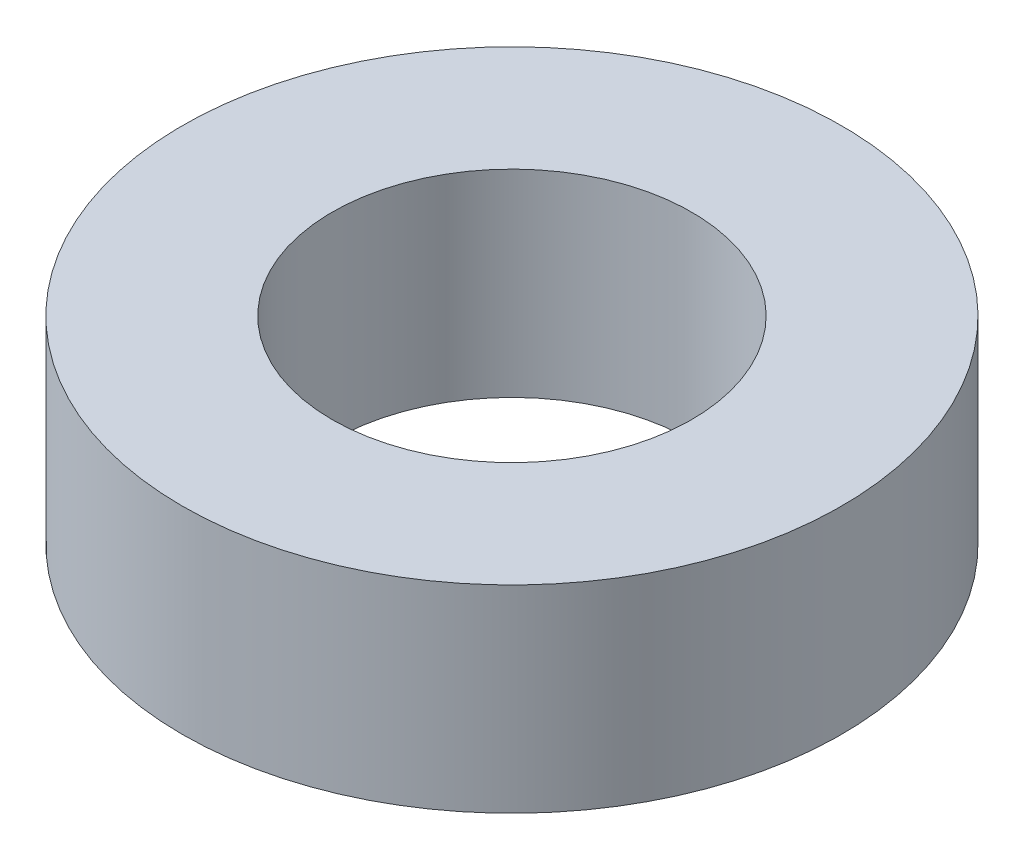
SolidWorks part; units mm, degrees
ref_plane "Front Plane" through (0, 0, 0) normal (0, 0, 1) x (1, 0, 0)
ref_plane "Top Plane" through (0, 0, 0) normal (0, 1, 0) x (1, 0, 0)
ref_plane "Right Plane" through (0, 0, 0) normal (1, 0, 0) x (0, 0, -1)
ref_axis "X-Axis" through (88.99, 0, 0) along (-1, 0, 0)
ref_axis "Y-Axis" through (0, 0, -88.99) along (0, 0, 1)
ref_axis "Z-Axis" through (0, -55, 0) along (0, 1, 0)
sketch "Sketch1" plane through (0, 0, 0) normal (0, 1, 0) x (1, 0, 0)
  circle A0 centre (0, 0) radius 6
  circle A1 centre (0, 0) radius 11
  dimension "D1" = 22
  dimension "D2" = 12
extrude "Boss-Extrude1" add sketch "Sketch1" along normal blind 6.6
